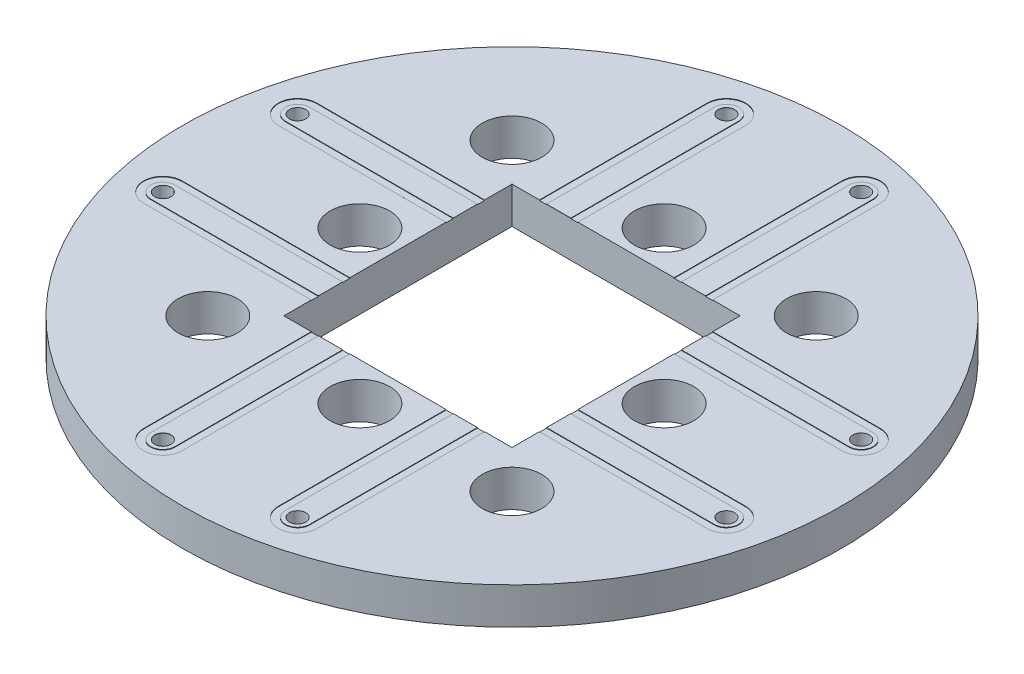
SolidWorks part; units mm, degrees
material "Ceramic Porcelain"
ref_plane "Front Plane" through (0, 0, 0) normal (0, 0, 1) x (1, 0, 0)
ref_plane "Top Plane" through (0, 0, 0) normal (0, 1, 0) x (1, 0, 0)
ref_plane "Right Plane" through (0, 0, 0) normal (1, 0, 0) x (0, 0, -1)
ref_axis "Y Axis" through (0, 0.0762, 0) along (0, -1, 0)
sketch "Boday Sketch" plane through (0, 0, 0) normal (0, 1, 0) x (1, 0, 0)
  circle A0 centre (0, 0) radius 11.557
  dimension "D1" = 23.114
extrude "Body" add sketch "Boday Sketch" against normal blind 1.27
sketch "Copper Sketch" plane through (0, 0, 0) normal (0, 1, 0) x (1, 0, 0)
  circle A0 centre (0, 0) radius 11.557
  dimension "D1" = 23.114
extrude "Copper" add sketch "Copper Sketch" along normal blind 0.0175
sketch "IO Hole Positions" plane through (0, 0, 0) normal (0, 1, 0) x (1, 0, 0)
  line L0 (-11.557, 0) -> (11.557, 0) construction
  circle A1 centre (0, 0) radius 11.557 construction
  point P1 (-2.3622, 9.8816)
  point P8 (-2.3622, -9.8816)
  dimension "D2" = 2.3622
sketch "Gap" plane through (0, 0, 0) normal (0, 1, 0) x (1, 0, 0)
  line L10 (-3.0372, 9.8816) -> (-3.0372, -9.8816)
  line L11 (-11.557, 0) -> (11.557, 0) construction
  line L12 (-3.0372, 0) -> (-1.6872, 0) construction
  line L13 (-1.6872, -9.8816) -> (-1.6872, 9.8816)
  arc A5 (-1.6872, 9.8816) -> (-3.0372, 9.8816) centre (-2.3622, 9.8816) ccw
  arc A6 (-1.6872, -9.8816) -> (-3.0372, -9.8816) centre (-2.3622, -9.8816) cw
  dimension "D1" = 0.675
sketch "Center Sketch" plane through (0, 0, 0) normal (0, 1, 0) x (1, 0, 0)
  line L6 (-2.7872, 9.8816) -> (-2.7872, -9.8816)
  line L7 (-11.557, 0) -> (11.557, 0) construction
  line L8 (-2.7872, 0) -> (-1.9372, 0) construction
  line L9 (-1.9372, -9.8816) -> (-1.9372, 9.8816)
  arc A3 (-1.9372, 9.8816) -> (-2.7872, 9.8816) centre (-2.3622, 9.8816) ccw
  arc A4 (-1.9372, -9.8816) -> (-2.7872, -9.8816) centre (-2.3622, -9.8816) cw
  dimension "D1" = 0.425
extrude "Gap Cut" cut sketch "Gap" along normal through all
extrude "Center" add sketch "Center Sketch" along normal blind 0.0175 separate body
sketch "IO Hole Sketch" plane through (0, 0, 0) normal (0, 1, 0) x (1, 0, 0)
  circle A1 centre (-2.3622, 9.8816) radius 0.287
  circle A3 centre (-2.3622, -9.8816) radius 0.287
  circle A4 centre (0, 0) radius 10.16 construction
  point P7 (0, 0)
  dimension "D1" = 0.574
  dimension "D2" = 0.574
  dimension "D3" = 20.32
  dimension "D4" = 2.3622
extrude "IO Hole" cut sketch "IO Hole Sketch" against normal through all and the other way through all
pattern_circular "Gap Cuts" count 4 over 360 about axis through (0, 0.0762, 0) along (0, -1, 0) of "Gap Cut"
pattern_circular "Centers" count 4 over 360 about axis through (0, 0.0762, 0) along (0, -1, 0) of "Center"
pattern_circular "IO Holes" count 4 over 360 about axis through (0, 0.0762, 0) along (0, -1, 0) of "IO Hole"
sketch "Pocket Sketch" plane through (0, 0, 0) normal (0, 1, 0) x (1, 0, 0)
  line L1 (-4, -4) -> (4, -4)
  line L2 (-4, -4) -> (-4, 4)
  line L3 (-4, 4) -> (4, 4)
  line L4 (4, -4) -> (4, 4)
  line L5 (-4, -4) -> (4, 4) construction
  line L6 (-4, 4) -> (4, -4) construction
  point P0 (0, 0)
  dimension "D1" = 8
  dimension "D2" = 8
extrude "Pocket" cut sketch "Pocket Sketch" against normal through all and the other way through all
sketch "Posts" plane through (0, 0, 0) normal (0, 1, 0) x (1, 0, 0)
  circle A0 centre (0, 5.334) radius 1.0414
  circle A8 centre (-5.334, 5.334) radius 1.0414
  point P0 (0, 5.334)
  point P4 (-5.334, 5.334)
  dimension "D2" = 2.0828
  dimension "D4" = 2.0828
  dimension "D1" = 5.334
  dimension "D3" = 7.5434
  dimension "D5" = 5.334
extrude "Post Cut" cut sketch "Posts" against normal through all and the other way through all
pattern_circular "Post Cuts" count 4 over 360 about axis through (0, 0.0762, 0) along (0, -1, 0) of "Post Cut"
equation "\"mount_d\"= 0.91in"
equation "\"dieletric_h\"= 0.05in"
equation "\"D1@Boday Sketch\" = \"mount_d\""
equation "\"D1@Body\" = \"dieletric_h\""
equation "\"screw_inner_r\"= 0.415in"
equation "\"io_r\"= 0.4in"
equation "\"io_hole_d\"= 0.574mm"
equation "\"W\"= 0.85mm"
equation "\"G\"= 0.25mm"
equation "\"copper_t\"= 17.5um"
equation "\"silicon_size\"= 8mm"
equation "\"D1@Center\" = \"copper_t\""
equation "\"D1@Copper\"=\"copper_t\""
equation "\"D1@Pocket Sketch\" = \"silicon_size\""
equation "\"D2@Pocket Sketch\" = \"silicon_size\""
equation "\"post_r1\"= 0.21in"
equation "\"post_r2\"= \"post_r1\" * sqr ( 2 )"
equation "\"D1@Posts\"=\"post_r1\""
equation "\"post_hole_size\"= 0.082in"
equation "\"D2@Posts\"=\"post_hole_size\""
equation "\"D3@Posts\"=\"post_r2\""
equation "\"D4@Posts\"=\"post_hole_size\""
equation "\"io_x\" = 0.093in"
equation "\"D1@IO Hole Positions\"=\"io_r\""
equation "\"D2@IO Hole Positions\"=\"io_x\""
equation "\"D1@IO Hole Sketch\"=\"io_hole_d\""
equation "\"D2@IO Hole Sketch\"=\"io_hole_d\""
equation "\"D1@Gap\"= \"W\" / 2 + \"G\""
equation "\"D1@Center Sketch\"=\"W\" / 2"
equation "\"D5@Posts\"=\"post_r1\""
equation "\"D4@IO Hole Sketch\"=\"io_x\""
